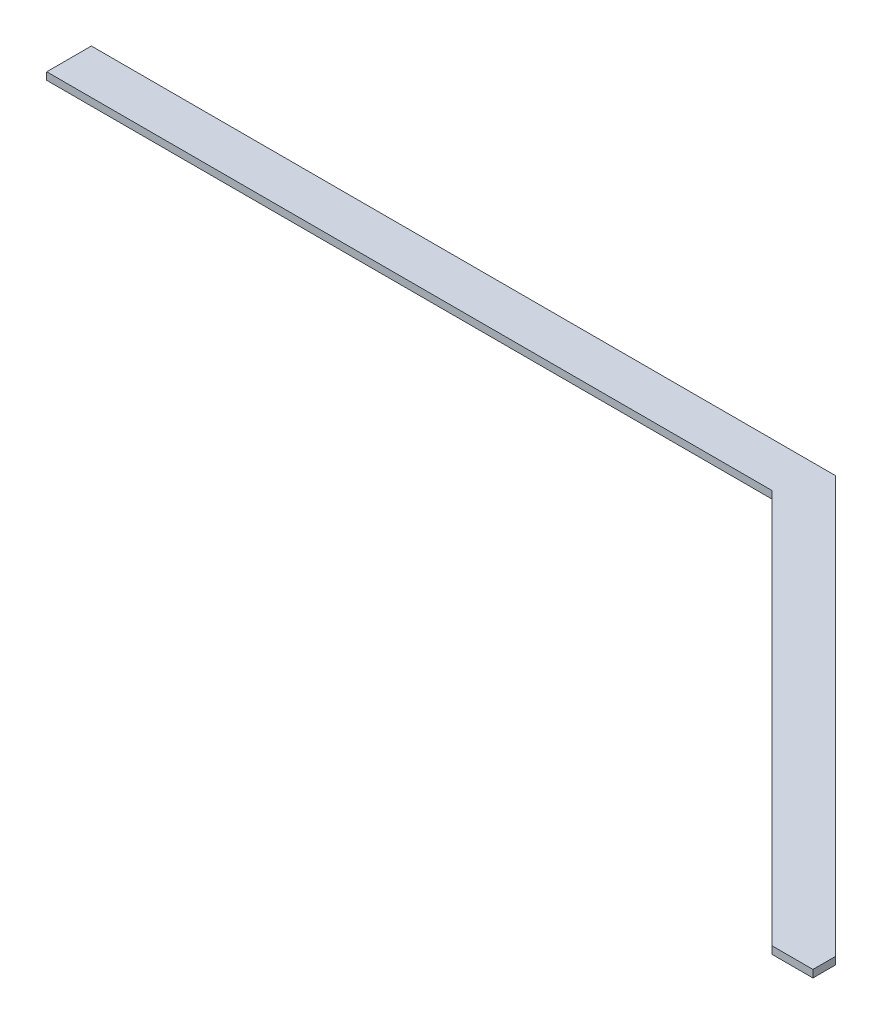
SolidWorks part; units mm, degrees
ref_plane "Front Plane" through (0, 0, 0) normal (0, 0, 1) x (1, 0, 0)
ref_plane "Top Plane" through (0, 0, 0) normal (0, 1, 0) x (1, 0, 0)
ref_plane "Right Plane" through (0, 0, 0) normal (1, 0, 0) x (0, 0, -1)
sketch "Sketch1" plane through (0, 0, 0) normal (0, 1, 0) x (1, 0, 0)
  line L1 (-300, 295) -> (-800, 295)
  line L2 (-800, 295) -> (-800, 265)
  line L3 (-800, 265) -> (-312.4264, 265)
  line L4 (-312.4264, 265) -> (-47.4264, 0)
  line L6 (-300, 295) -> (-20, 15)
  line L11 (-20, 15) -> (-20, 0)
  line L12 (-20, 0) -> (-47.4264, 0)
  point P0 (0, 0)
  dimension "D1" = 30
  dimension "D2" = 30
  dimension "D3" = 500
  dimension "D4" = 15
  dimension "D5" = 135
  dimension "D6" = 20
  dimension "D7" = 265
extrude "Boss-Extrude1" add sketch "Sketch1" along normal blind 5
